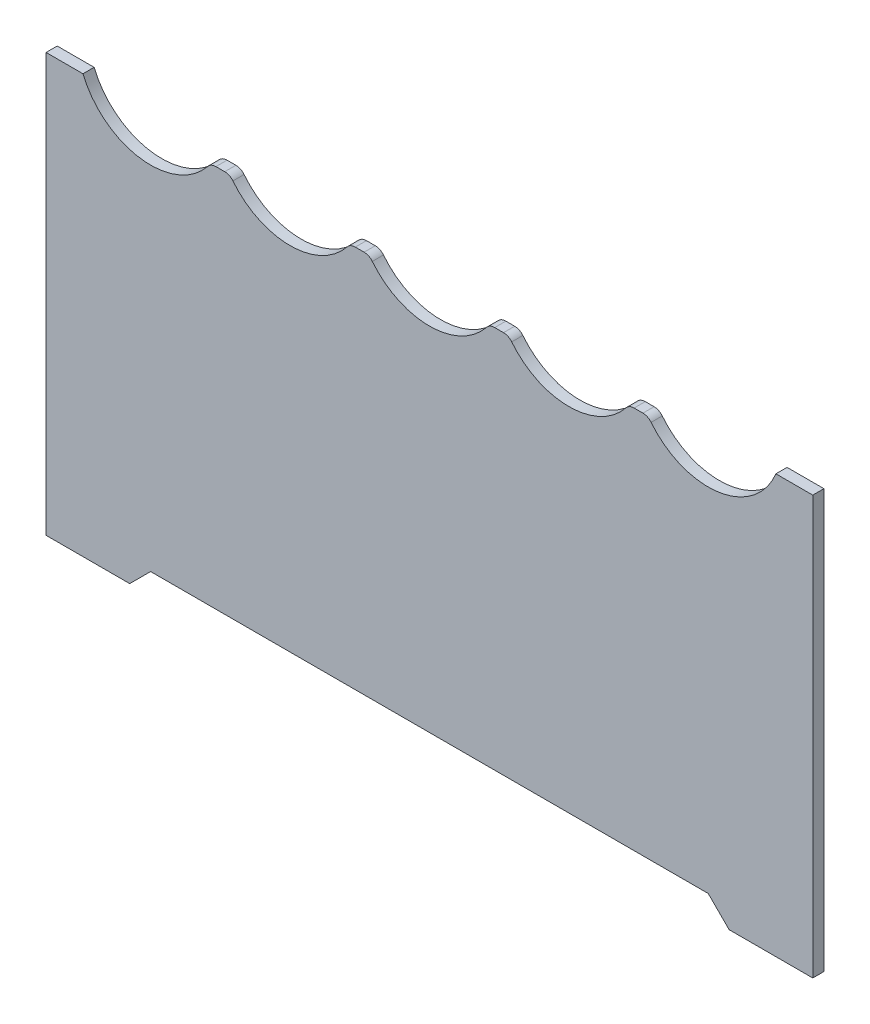
SolidWorks part; units mm, degrees
ref_plane "Front Plane" through (0, 0, 0) normal (0, 0, 1) x (1, 0, 0)
ref_plane "Top Plane" through (0, 0, 0) normal (0, 1, 0) x (1, 0, 0)
ref_plane "Right Plane" through (0, 0, 0) normal (1, 0, 0) x (0, 0, -1)
sketch "Sketch2" plane through (0, 0, 0) normal (0, 0, 1) x (1, 0, 0)
  line L0 (-43, 0) -> (-40, 3)
  line L1 (-55, 60) -> (-49.7082, 60)
  line L2 (-55, 60) -> (-55, 0)
  line L3 (-55, 0) -> (-43, 0)
  line L4 (55, 60) -> (55, 0)
  line L5 (-40, 3) -> (40, 3)
  line L6 (-10.6325, 58) -> (-9.3675, 58)
  line L7 (29.3675, 58) -> (30.6325, 58)
  line L8 (49.7082, 60) -> (55, 60)
  line L9 (-30.6325, 58) -> (-29.3675, 58)
  line L10 (9.3675, 58) -> (10.6325, 58)
  line L11 (40, 3) -> (43, 0)
  line L12 (43, 0) -> (55, 0)
  arc A2 (-49.7082, 60) -> (-31.8034, 57.4375) centre (-40, 64) ccw
  arc A5 (31.8034, 57.4375) -> (49.7082, 60) centre (40, 64) ccw
  arc A6 (11.8034, 57.4375) -> (28.1966, 57.4375) centre (20, 64) ccw
  arc A7 (-8.1966, 57.4375) -> (8.1966, 57.4375) centre (0, 64) ccw
  arc A8 (-30.6325, 58) -> (-31.8034, 57.4375) centre (-30.6325, 56.5) ccw
  arc A9 (-28.1966, 57.4375) -> (-11.8034, 57.4375) centre (-20, 64) ccw
  arc A10 (-29.3675, 58) -> (-28.1966, 57.4375) centre (-29.3675, 56.5) cw
  arc A11 (-11.8034, 57.4375) -> (-10.6325, 58) centre (-10.6325, 56.5) cw
  arc A12 (-9.3675, 58) -> (-8.1966, 57.4375) centre (-9.3675, 56.5) cw
  arc A13 (8.1966, 57.4375) -> (9.3675, 58) centre (9.3675, 56.5) cw
  arc A14 (10.6325, 58) -> (11.8034, 57.4375) centre (10.6325, 56.5) cw
  arc A15 (28.1966, 57.4375) -> (29.3675, 58) centre (29.3675, 56.5) cw
  arc A16 (31.8034, 57.4375) -> (30.6325, 58) centre (30.6325, 56.5) ccw
  point P25 (-11.3832, 58)
  point P32 (8.6168, 58)
  point P37 (28.6168, 58)
  point P40 (0, 3)
  dimension "D3" = 1.5
  dimension "D5" = 10.5
  dimension "D1" = 60
  dimension "D2" = 110
  dimension "D4" = 4
  dimension "D7" = 6
  dimension "D6" = 20
  dimension "D8" = 20
  dimension "D9" = 20
  dimension "D10" = 20
  dimension "D11" = 135
  dimension "D12" = 3
  dimension "D13" = 80
extrude "Boss-Extrude1" add sketch "Sketch2" along normal blind 1.6
